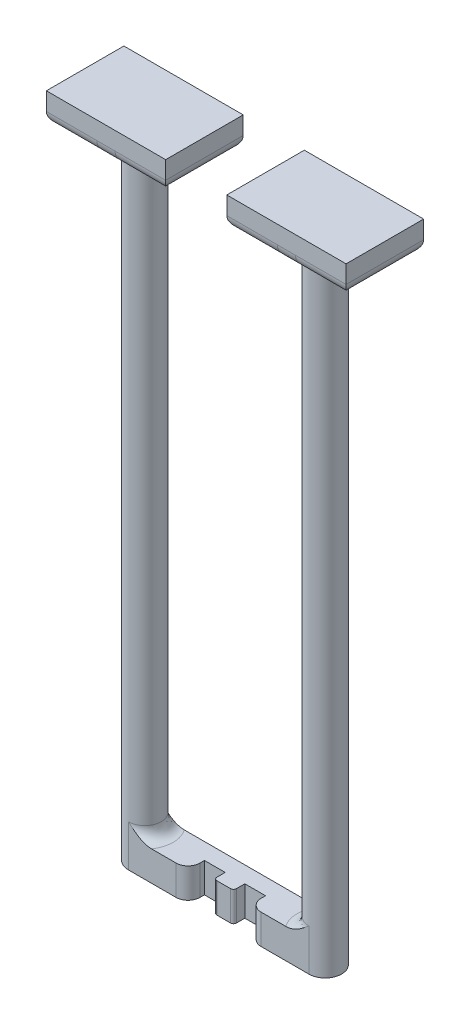
SolidWorks part; units mm, degrees
note: The reader was unsure of these and kept them because the rebuilt part matched: shared geometry of "Sketch1<5>", "Sketch1<6>".
ref_plane "Front Plane" through (0, 0, 0) normal (0, 0, 1) x (1, 0, 0)
ref_plane "Top Plane" through (0, 0, 0) normal (0, 1, 0) x (1, 0, 0)
ref_plane "Right Plane" through (0, 0, 0) normal (1, 0, 0) x (0, 0, -1)
sketch "Sketch1" plane through (0, 0, 0) normal (0, 1, 0) x (1, 0, 0)
  line L0 (0, 0) -> (15.125, 0) construction
  line L1 (0, 0) -> (0, 6.3857) construction
  line L2 (5.125, 6.5) -> (25.125, 6.5)
  line L3 (5.125, 6.5) -> (5.125, -6.5)
  line L4 (5.125, -6.5) -> (25.125, -6.5)
  line L5 (25.125, 6.5) -> (25.125, -6.5)
  line L6 (5.125, 6.5) -> (25.125, -6.5) construction
  line L7 (5.125, -6.5) -> (25.125, 6.5) construction
  line L8 (-25.125, 6.5) -> (-25.125, -6.5)
  line L9 (-5.125, -6.5) -> (-25.125, -6.5)
  line L10 (-5.125, 6.5) -> (-5.125, -6.5)
  line L11 (-5.125, 6.5) -> (-25.125, 6.5)
  line L12 (-5.125, -6.5) -> (-25.125, 6.5) construction
  line L13 (-5.125, 6.5) -> (-25.125, -6.5) construction
  line L14 (-15.125, -2.75) -> (15.125, -2.75)
  line L15 (15.125, -2.75) -> (15.125, 2.75)
  line L16 (15.125, 2.75) -> (-15.125, 2.75)
  line L17 (-15.125, 2.75) -> (-15.125, -2.75)
  line L19 (5.125, 0) -> (-5.125, 0)
  line L20 (5.125, 0) -> (5.125, 2.75)
  line L21 (5.125, 2.75) -> (-5.125, 2.75)
  line L22 (-5.125, 0) -> (-5.125, 2.75)
  line L23 (5.125, 0) -> (-5.125, 2.75) construction
  line L24 (5.125, 2.75) -> (-5.125, 0) construction
  line L25 (1.65, 0) -> (-1.65, 0)
  line L26 (1.65, 0) -> (1.65, -1.9)
  line L27 (1.65, -1.9) -> (-1.65, -1.9)
  line L28 (-1.65, 0) -> (-1.65, -1.9)
  line L29 (1.65, 0) -> (-1.65, -1.9) construction
  line L30 (1.65, -1.9) -> (-1.65, 0) construction
  circle A0 centre (15.125, 0) radius 2.75
  circle A1 centre (-15.125, 0) radius 2.75
  point P12 (-15.125, 0)
  point P24 (0, 1.375)
  point P29 (0, -0.95)
  point P30 (0, 0)
  dimension "D4" = 5.5
  dimension "D1" = 13
  dimension "D2" = 20
  dimension "D3" = 30.25
  dimension "D5" = 1.9
  dimension "D6" = 3.3
extrude "Boss-Extrude1" add sketch "Sketch1" along normal blind 5 contours L14 A1 L16 L10 L11 L8 L9 | A0 L14 L3 L4 L5 L2 L16 | L15 A0 | L15 A0 | A0 L16 L3 L14 | L16 A1 L14 L10 | A1 L17
extrude "Boss-Extrude2" add sketch "Sketch1<5>" against normal blind 105 contours A1 | A0 | A1 L17 | L15 A0
sketch "Sketch1<5>" plane through (0, 0, 0) normal (0, 1, 0) x (1, 0, 0) same geometry as "Sketch1"
extrude "Boss-Extrude3" add sketch "Sketch1<6>" along normal blind 5 from surface contours L3 L16 L10 L14 | L16 A1 L14 L10 | A0 L16 L3 L14 | L15 A0 | A1 L17 | L19 L28 L27 L26 starting at face at (-15.125, 0, 2.75)
sketch "Sketch1<6>" plane through (0, 0, 0) normal (0, 1, 0) x (1, 0, 0) same geometry as "Sketch1"
fillet "Fillet2" radius 2 2 edges at (15.125, 0, 2.75) (-15.125, 0, 2.75)
fillet "Fillet3" radius 2 8 edges at (25.125, 0, 0) (5.125, 0, 0) (-5.125, 0, 0) (-25.125, 0, 0) (15.125, 0, 6.5) (15.125, 0, -6.5) (-15.125, 0, 6.5) (-15.125, 0, -6.5)
fillet "Fillet4" radius 2 2 edges at (-12.375, -100, 0) (12.375, -100, 0)
fillet "Fillet5" radius 2 2 edges at (5.125, -102.5, 2.75) (-5.125, -102.5, 2.75)
fillet "Fillet6" radius 0.5 2 edges at (1.65, -102.5, 1.9) (-1.65, -102.5, 1.9)
